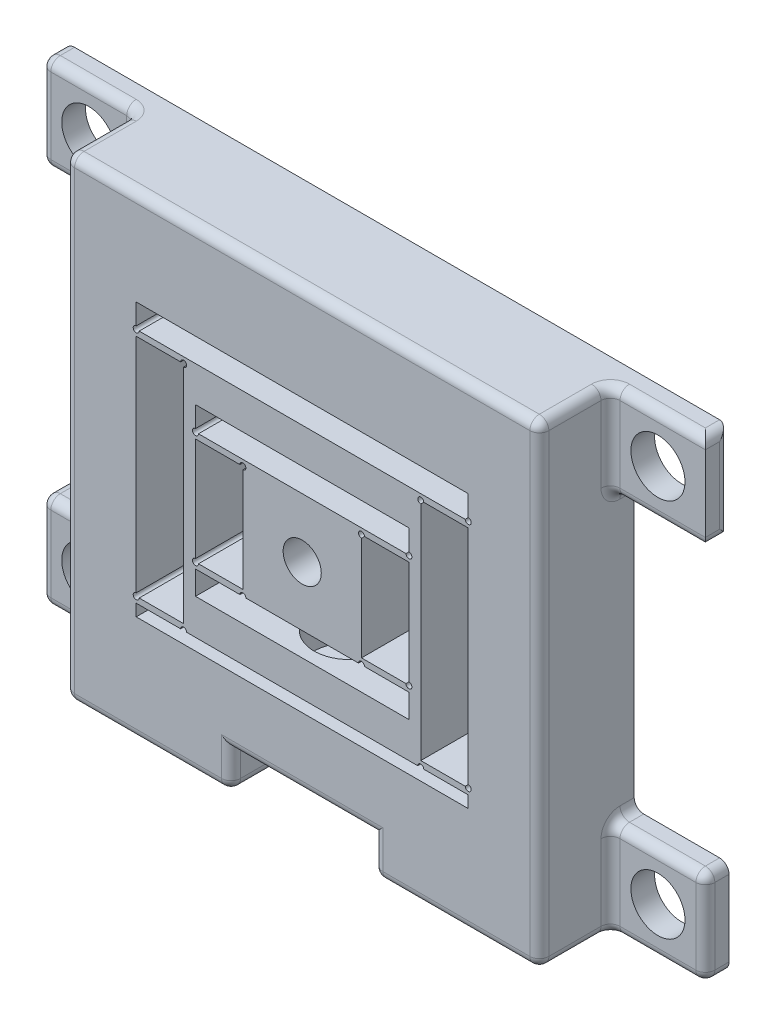
SolidWorks part; units mm, degrees
ref_plane "Front Plane" through (0, 0, 0) normal (0, 0, 1) x (1, 0, 0)
ref_plane "Top Plane" through (0, 0, 0) normal (0, 1, 0) x (1, 0, 0)
ref_plane "Right Plane" through (0, 0, 0) normal (1, 0, 0) x (0, 0, -1)
sketch "Sketch1" plane through (0, 0, 0) normal (0, 0, 1) x (1, 0, 0)
  line L1 (-31.75, -31.75) -> (31.75, -31.75)
  line L2 (-31.75, -31.75) -> (-31.75, 31.75)
  line L3 (-31.75, 31.75) -> (31.75, 31.75)
  line L4 (31.75, -31.75) -> (31.75, 31.75)
  line L5 (-31.75, -31.75) -> (31.75, 31.75) construction
  line L6 (-31.75, 31.75) -> (31.75, -31.75) construction
  point P0 (0, 0)
  dimension "D1" = 63.5
  dimension "D2" = 63.5
extrude "Boss-Extrude1" add sketch "Sketch1" along normal blind 12.7
sketch "Sketch2" plane through (0, 0, 12.7) normal (0, 0, 1) x (1, 0, 0)
  line L1 (-7.9375, -7.9375) -> (7.9375, -7.9375)
  line L2 (-7.9375, -7.9375) -> (-7.9375, 7.9375)
  line L3 (-7.9375, 7.9375) -> (7.9375, 7.9375)
  line L4 (7.9375, -7.9375) -> (7.9375, 7.9375)
  line L5 (-7.9375, -7.9375) -> (7.9375, 7.9375) construction
  line L6 (-7.9375, 7.9375) -> (7.9375, -7.9375) construction
  line L7 (-14.2875, -11.1125) -> (14.2875, -11.1125)
  line L8 (-14.2875, -11.1125) -> (-14.2875, 11.1125)
  line L9 (-14.2875, 11.1125) -> (14.2875, 11.1125)
  line L10 (14.2875, -11.1125) -> (14.2875, 11.1125)
  line L11 (-14.2875, -11.1125) -> (14.2875, 11.1125) construction
  line L12 (-14.2875, 11.1125) -> (14.2875, -11.1125) construction
  point P5 (0, 0)
  dimension "D1" = 15.875
  dimension "D2" = 15.875
  dimension "D3" = 3.175
  dimension "D4" = 3.175
  dimension "D5" = 6.35
  dimension "D6" = 6.35
extrude "Cut-Extrude1" cut sketch "Sketch2" against normal through all
sketch "Sketch3" plane through (0, 0, 12.7) normal (0, 0, 1) x (1, 0, 0)
  line L0 (-22.225, 19.05) -> (22.225, 19.05)
  line L1 (-15.875, -15.875) -> (15.875, -15.875)
  line L2 (-15.875, -15.875) -> (-15.875, 15.875)
  line L3 (-15.875, 15.875) -> (15.875, 15.875)
  line L4 (15.875, -15.875) -> (15.875, 15.875)
  line L5 (-15.875, -15.875) -> (15.875, 15.875) construction
  line L6 (-15.875, 15.875) -> (15.875, -15.875) construction
  line L7 (22.225, -17.4625) -> (22.225, 19.05)
  line L8 (-22.225, -17.4625) -> (22.225, -17.4625)
  line L9 (-22.225, -17.4625) -> (-22.225, 19.05)
  point P0 (0, 0)
  dimension "D1" = 31.75
  dimension "D2" = 31.75
  dimension "D3" = 3.175
  dimension "D4" = 6.35
  dimension "D5" = 6.35
  dimension "D6" = 1.5875
extrude "Cut-Extrude2" cut sketch "Sketch3" against normal through all
sketch "Sketch4" plane through (0, 0, 12.7) normal (0, 0, 1) x (1, 0, 0)
  line L0 (-7.9375, 7.9375) -> (-14.2875, 7.9375)
  line L1 (7.9375, 7.9375) -> (-7.9375, 7.9375) construction
  line L2 (-7.9375, 7.9375) -> (-7.9375, -7.9375) construction
  line L4 (-14.2875, 7.9375) -> (-14.2875, 7.1375)
  line L5 (-14.2875, 7.1375) -> (-7.9375, 7.1375)
  line L6 (-7.9375, 7.1375) -> (-7.9375, 7.9375)
  line L7 (-15.875, 15.875) -> (-22.225, 15.875)
  line L8 (-22.225, 19.05) -> (-22.225, -17.4625) construction
  line L9 (-22.225, 15.875) -> (-22.225, 15.075)
  line L10 (-22.225, 15.075) -> (-15.875, 15.075)
  line L11 (-15.875, 15.875) -> (-15.875, -15.875) construction
  line L12 (-15.875, 15.075) -> (-15.875, 15.875)
  line L13 (0, 0) -> (0, 19.05) construction
  line L14 (22.225, 19.05) -> (-22.225, 19.05) construction
  line L15 (0, 0) -> (-22.225, 0) construction
  line L16 (15.875, 15.075) -> (15.875, 15.875)
  line L17 (22.225, 15.075) -> (15.875, 15.075)
  line L18 (22.225, 15.875) -> (22.225, 15.075)
  line L19 (15.875, 15.875) -> (22.225, 15.875)
  line L20 (7.9375, 7.1375) -> (7.9375, 7.9375)
  line L21 (14.2875, 7.1375) -> (7.9375, 7.1375)
  line L22 (14.2875, 7.9375) -> (14.2875, 7.1375)
  line L23 (7.9375, 7.9375) -> (14.2875, 7.9375)
  line L24 (7.9375, -7.9375) -> (14.2875, -7.9375)
  line L25 (14.2875, -7.9375) -> (14.2875, -7.1375)
  line L26 (14.2875, -7.1375) -> (7.9375, -7.1375)
  line L27 (7.9375, -7.1375) -> (7.9375, -7.9375)
  line L28 (15.875, -15.875) -> (22.225, -15.875)
  line L29 (22.225, -15.875) -> (22.225, -15.075)
  line L30 (22.225, -15.075) -> (15.875, -15.075)
  line L31 (15.875, -15.075) -> (15.875, -15.875)
  line L32 (-15.875, -15.075) -> (-15.875, -15.875)
  line L33 (-22.225, -15.075) -> (-15.875, -15.075)
  line L34 (-22.225, -15.875) -> (-22.225, -15.075)
  line L35 (-15.875, -15.875) -> (-22.225, -15.875)
  line L36 (-7.9375, -7.1375) -> (-7.9375, -7.9375)
  line L37 (-14.2875, -7.1375) -> (-7.9375, -7.1375)
  line L38 (-14.2875, -7.9375) -> (-14.2875, -7.1375)
  line L39 (-7.9375, -7.9375) -> (-14.2875, -7.9375)
  line L40 (-14.2875, 11.1125) -> (-14.2875, -11.1125) construction
  dimension "D1" = 0.8
  dimension "D2" = 0.8
extrude "Boss-Extrude3" add sketch "Sketch4" against normal up to surface (12.7 mm away) up to face at (0, 0.7938, 0)
sketch "Sketch5" plane through (0, 0, 12.7) normal (0, 0, 1) x (1, 0, 0)
  line L0 (-15.875, -15.075) -> (-15.875, -15.875) construction
  line L1 (0, 0) -> (0, 11.1125) construction
  line L3 (0, 11.1125) -> (14.2875, 0) construction
  line L5 (14.2875, 0) -> (0, 0) construction
  line L6 (-14.2875, -7.9375) -> (14.2875, -7.9375) construction
  line L7 (-7.9375, -7.1375) -> (-7.9375, -7.9375) construction
  line L8 (-22.225, -15.875) -> (22.225, -15.875) construction
  line L10 (7.9375, -7.1375) -> (7.9375, -7.9375) construction
  line L11 (15.875, -15.075) -> (15.875, -15.875) construction
  line L14 (14.2875, -7.1375) -> (14.2875, 7.1375) construction
  line L15 (14.2875, 11.1125) -> (-14.2875, 11.1125) construction
  line L16 (14.2875, 7.9375) -> (-14.2875, 7.9375) construction
  line L17 (-14.2875, 11.1125) -> (-14.2875, 7.9375) construction
  circle A0 centre (-22.225, 15.875) radius 0.4
  circle A1 centre (-15.875, 15.075) radius 0.4
  circle A2 centre (7.9375, 7.1375) radius 0.4
  circle A3 centre (-14.2875, 7.9375) radius 0.4
  circle A4 centre (-7.9375, 7.1375) radius 0.4
  circle A5 centre (14.2875, 7.9375) radius 0.4
  circle A6 centre (15.875, 15.075) radius 0.4
  circle A7 centre (22.225, 15.875) radius 0.4
  circle A8 centre (-7.9375, -7.9375) radius 0.4
  circle A9 centre (-14.2875, -7.1375) radius 0.4
  circle A10 centre (-22.225, -15.075) radius 0.4
  circle A11 centre (-15.875, -15.875) radius 0.4
  circle A12 centre (15.875, -15.875) radius 0.4
  circle A13 centre (22.225, -15.075) radius 0.4
  circle A14 centre (14.2875, -7.1375) radius 0.4
  circle A15 centre (7.9375, -7.9375) radius 0.4
  dimension "D1" = 0.8
  dimension "D2" = 0.8
  dimension "D3" = 0.8
  dimension "D4" = 0.8
  dimension "D5" = 0.8
  dimension "D6" = 0.8
  dimension "D7" = 0.8
  dimension "D8" = 0.8
extrude "Cut-Extrude3" cut sketch "Sketch5" against normal through all
sketch "Sketch6" plane through (0, -31.75, 0) normal (0, -1, 0) x (-1, 0, 0)
  line L0 (31.75, -6.35) -> (-31.75, -6.35) construction
  line L1 (31.75, -12.7) -> (31.75, 0) construction
  line L2 (-31.75, -12.7) -> (-31.75, 0) construction
  circle A0 centre (0, -6.35) radius 4.2164
  dimension "D1" = 8.4328
extrude "Cut-Extrude4" cut sketch "Sketch6" against normal up to surface (14.2875 mm away) up to face at (0, -17.4625, 6.35)
sketch "Sketch8" plane through (0, -15.875, 0) normal (0, -1, 0) x (-1, 0, 0)
  circle A0 centre (0, -6.35) radius 4.7625
  dimension "D1" = 9.525
extrude "Cut-Extrude6" cut sketch "Sketch8" against normal up to next
sketch "Sketch10" plane through (0, 0, 12.7) normal (0, 0, 1) x (1, 0, 0)
  circle A0 centre (0, 0) radius 2.5527
  dimension "D1" = 5.1054
extrude "Cut-Extrude8" cut sketch "Sketch10" against normal through all
sketch "Sketch11" plane through (0, -31.75, 0) normal (0, -1, 0) x (-1, 0, 0)
  line L0 (0, -10.5664) -> (0, -2.1336) construction
  circle A0 centre (0, -6.35) radius 4.2164 construction
ref_plane "Plane1" through (15.875, -15.875, 0) normal (0.7071, -0.7071, 0) x (0, 0, -1)
sketch "Sketch12" plane through (15.875, -15.875, 0) normal (0.7071, -0.7071, 0) x (0, 0, -1)
  line L0 (-12.7, -44.9013) -> (-12.7, 0) construction
  circle A0 centre (-6.35, -11.0206) radius 1.1303
  ellipse E0 centre (-6.35, -22.4506) end of major axis (-10.5664, -22.4506) minor radius 2.9814 construction
  dimension "D1" = 2.2606
  dimension "D2" = 11.43
  dimension "D3" = 6.35
extrude "Cut-Extrude9" cut sketch "Sketch12" along normal through all and the other way blind 7.62
mirror "Mirror1" about plane through (0, 0, 0) normal (1, 0, 0) of "Cut-Extrude9"
sketch "Sketch19" plane through (0, 0, 0) normal (0, 0, -1) x (-1, 0, 0)
  line L0 (31.75, 31.75) -> (31.75, -31.75) construction
  line L1 (44.45, -19.05) -> (31.75, -19.05)
  line L2 (44.45, -19.05) -> (44.45, -31.75)
  line L3 (44.45, -31.75) -> (31.75, -31.75)
  line L4 (31.75, -19.05) -> (31.75, -31.75)
  line L5 (44.45, -19.05) -> (31.75, -31.75) construction
  line L6 (44.45, -31.75) -> (31.75, -19.05) construction
  line L7 (0, 0) -> (38.1, 0) construction
  line L8 (44.45, 31.75) -> (31.75, 31.75)
  line L9 (44.45, 31.75) -> (44.45, 19.05)
  line L10 (44.45, 19.05) -> (31.75, 19.05)
  line L11 (31.75, 31.75) -> (31.75, 19.05)
  line L12 (44.45, 31.75) -> (31.75, 19.05) construction
  line L13 (44.45, 19.05) -> (31.75, 31.75) construction
  line L14 (38.1, -25.4) -> (38.1, 25.4) construction
  line L15 (0, 0) -> (0, 31.75) construction
  line L16 (-31.75, 31.75) -> (31.75, 31.75) construction
  line L17 (-44.45, 31.75) -> (-44.45, 19.05)
  line L18 (-44.45, 31.75) -> (-31.75, 31.75)
  line L19 (-31.75, 31.75) -> (-31.75, 19.05)
  line L20 (-44.45, 19.05) -> (-31.75, 19.05)
  line L21 (-44.45, -19.05) -> (-44.45, -31.75)
  line L22 (-44.45, -31.75) -> (-31.75, -31.75)
  line L23 (-31.75, -19.05) -> (-31.75, -31.75)
  line L24 (-44.45, -19.05) -> (-31.75, -19.05)
  point P0 (38.1, -25.4)
  point P7 (38.1, 25.4)
  dimension "D1" = 12.7
  dimension "D2" = 12.7
  dimension "D3" = 38.1
  dimension "D4" = 50.8
extrude "Boss-Extrude4" add sketch "Sketch19" against normal blind 3.175
sketch "Sketch9" plane through (0, 0, 12.7) normal (0, 0, 1) x (1, 0, 0)
  line L1 (-38.1, -25.4) -> (38.1, -25.4) construction
  line L2 (-38.1, -25.4) -> (-38.1, 25.4) construction
  line L3 (-38.1, 25.4) -> (38.1, 25.4) construction
  line L4 (38.1, -25.4) -> (38.1, 25.4) construction
  line L5 (-38.1, -25.4) -> (38.1, 25.4) construction
  line L6 (-38.1, 25.4) -> (38.1, -25.4) construction
  circle A0 centre (-38.1, 25.4) radius 3.6195
  circle A1 centre (38.1, 25.4) radius 3.6195
  circle A2 centre (38.1, -25.4) radius 3.6195
  circle A3 centre (-38.1, -25.4) radius 3.6195
  point P0 (0, 0)
  dimension "D3" = 7.239
  dimension "D4" = 7.239
  dimension "D5" = 7.239
  dimension "D6" = 7.239
  dimension "D1" = 76.2
  dimension "D2" = 50.8
extrude "Cut-Extrude7" cut sketch "Sketch9" against normal through all
fillet "Fillet3" radius 1.27 36 edges at (44.45, 31.75, 1.5875) (31.75, 19.05, 1.5875) (44.45, 19.05, 1.5875) (-31.75, 19.05, 1.5875) (-44.45, 19.05, 1.5875) (-44.45, 31.75, 1.5875) (-44.45, -31.75, 1.5875) (-44.45, -19.05, 1.5875) (-31.75, -19.05, 1.5875) (31.75, -19.05, 1.5875) (44.45, -19.05, 1.5875) (44.45, -31.75, 1.5875) (31.75, -31.75, 7.9375) (-38.1, 31.75, 3.175) (-38.1, -31.75, 3.175) (38.1, -31.75, 3.175) (-31.75, 25.4, 3.175) (-31.75, -25.4, 3.175) (31.75, -25.4, 3.175) (31.75, 25.4, 3.175) (-44.45, 25.4, 3.175) (-38.1, 19.05, 3.175) (-44.45, -25.4, 3.175) (-38.1, -19.05, 3.175) (44.45, -25.4, 3.175) (38.1, -19.05, 3.175) (38.1, 19.05, 3.175) (44.45, 25.4, 0) (38.1, 31.75, 3.175) (0, 31.75, 12.7) (-31.75, 0, 12.7) (0, -31.75, 12.7) (31.75, 0, 12.7) (31.75, 31.75, 7.9375) (-31.75, 31.75, 7.9375) (-31.75, -31.75, 7.9375)
sketch "Sketch20" plane through (0, -31.75, 0) normal (0, -1, 0) x (-1, 0, 0)
  line L0 (43.18, 0) -> (-43.18, 0) construction
  line L1 (9.525, 0) -> (-9.525, 0)
  line L2 (9.525, 0) -> (9.525, -12.7)
  line L3 (9.525, -12.7) -> (-9.525, -12.7)
  line L4 (-9.525, 0) -> (-9.525, -12.7)
  line L5 (9.525, 0) -> (-9.525, -12.7) construction
  line L6 (9.525, -12.7) -> (-9.525, 0) construction
  line L7 (30.48, -12.7) -> (-30.48, -12.7) construction
  point P0 (0, -6.35)
  point P6 (-6.4434, 0)
  point P9 (0, 0)
  dimension "D1" = 19.05
extrude "Cut-Extrude10" cut sketch "Sketch20" against normal blind 5.08
fillet "Fillet4" radius 1.27 7 edges at (9.525, -31.75, 5.715) (9.525, -31.378, 12.328) (-9.525, -31.75, 5.715) (-9.525, -31.378, 12.328) (9.525, -28.575, 12.7) (-9.525, -28.575, 12.7) (0, -26.67, 12.7)
